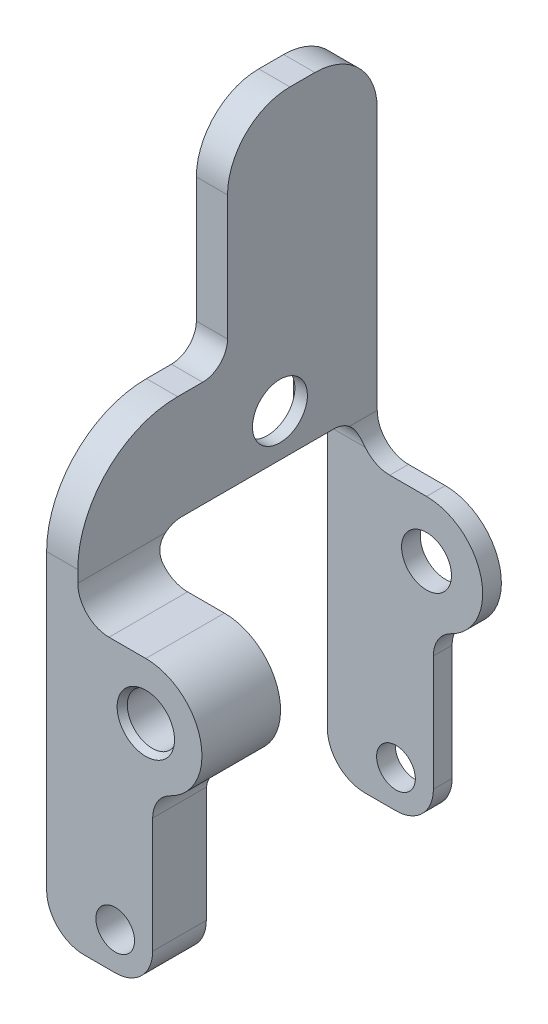
SolidWorks part; units mm, degrees
material "aluminio"
ref_plane "Alzado" through (0, 0, 0) normal (0, 0, 1) x (1, 0, 0)
ref_plane "Planta" through (0, 0, 0) normal (0, 1, 0) x (1, 0, 0)
ref_plane "Vista lateral" through (0, 0, 0) normal (1, 0, 0) x (0, 0, -1)
sketch "Croquis1" plane through (0, 0, 0) normal (0, 0, 1) x (1, 0, 0)
  line L0 (-5.5, 0) -> (-5.5, 31.5)
  line L1 (-5.5, 31.5) -> (-3, 31.5)
  line L2 (-3, 31.5) -> (-3, 20.05)
  line L3 (-3, 20.05) -> (2.45, 20.05)
  line L4 (0, -3) -> (-2.5, -3)
  line L5 (3, 0) -> (3, 11.0837)
  arc A0 (-5.5, 0) -> (-2.5, -3) centre (-2.5, 0) ccw
  arc A1 (3, 11.0837) -> (2.45, 20.05) centre (2.45, 15.55) ccw
  circle A2 centre (2.45, 15.55) radius 2
  circle A3 centre (0, 0) radius 1.55
  arc A5 (0, -3) -> (3, 0) centre (0, 0) ccw
  dimension "D1" = 5.5
  dimension "D2" = 31.5
  dimension "D4" = 9
  dimension "D7" = 4
  dimension "D8" = 3.1
  dimension "D9" = 3
  dimension "D12" = 3
  dimension "D3" = 2.5
  dimension "D5" = 15.55
  dimension "D6" = 2.45
extrude "Saliente-Extruir1" add sketch "Croquis1" along normal blind 24
sketch "Croquis2" plane through (-5.5, 0, 0) normal (-1, 0, 0) x (0, 0, 1)
  line L0 (24, -3) -> (0, -3) construction
  line L1 (1.5, -3) -> (19.7, -3)
  line L2 (1.5, -3) -> (1.5, 23)
  line L3 (1.5, 23) -> (17.7, 23)
  line L4 (17.7, 23) -> (17.7, 11)
  line L5 (1.5, 23) -> (0, 23) construction
  line L6 (0, 31.5) -> (0, 0) construction
  line L7 (0, 0) -> (0, -3) construction
  line L10 (17.7, 11) -> (19.7, 11)
  line L11 (19.7, 11) -> (19.7, -3)
  dimension "D1" = 16.2
  dimension "D2" = 26
  dimension "D3" = 1.5
  dimension "D4" = 12
  dimension "D5" = 2
extrude "Cortar-Extruir1" cut sketch "Croquis2" against normal blind 20
fillet "Redondeo1" radius 8 2 edges at (-4.25, 31.5, 0) (-4.25, 31.5, 24)
fillet "Redondeo2" radius 2 3 edges at (-1.25, 11, 19.7) (-4.25, 23, 17.7) (-4.25, 23, 1.5)
fillet "Redondeo5" radius 2.5 4 edges at (3, 11.0837, 0.75) (-3, 20.05, 20.85) (3, 11.0837, 20.85) (-3, 20.05, 0.75)
sketch "Croquis3" plane through (-5.5, 0, 0) normal (-1, 0, 0) x (0, 0, 1)
  line L0 (16, 31.5) -> (8, 31.5) construction
  line L1 (0, 23.5) -> (0, 0) construction
  circle A0 centre (7.8, 26.4) radius 2.2
  dimension "D1" = 4.4
  dimension "D2" = 5.1
  dimension "D3" = 7.8
extrude "Cortar-Extruir2" cut sketch "Croquis3" against normal blind 20
sketch "Croquis4" plane through (0, 23, 0) normal (0, -1, 0) x (1, 0, 0)
  line L0 (-5.5, 15.7) -> (-5.5, 3.5) construction
  line L1 (-5.5, 11.4) -> (-4, 11.4)
  line L2 (-5.5, 11.4) -> (-5.5, 4.2)
  line L3 (-5.5, 4.2) -> (-4, 4.2)
  line L4 (-4, 11.4) -> (-4, 4.2)
  line L5 (-5.5, 10) -> (-5.5, 5.6) construction
  point P8 (-5.5, 7.8)
  dimension "D1" = 7.2
  dimension "D2" = 1.5
extrude "Cortar-Extruir3" cut sketch "Croquis4" against normal blind 20
sketch "Croquis5" plane through (-5.5, 0, 0) normal (-1, 0, 0) x (0, 0, 1)
  line L0 (0, 23.5) -> (0, 48.5)
  line L1 (0, 48.5) -> (12, 48.5)
  line L2 (12, 30) -> (4.2, 30)
  line L5 (12, 30) -> (12, 48.5)
  line L6 (4.2, 30.5399) -> (4.2, 23) construction
  line L7 (4.2, 30) -> (0, 23.5)
  line L8 (8, 31.5) -> (11.4, 31.5) construction
  line L9 (16, 31.5) -> (11.4, 31.5) construction
  dimension "D1" = 4
  dimension "D2" = 1.5
  dimension "D3" = 17
extrude "Saliente-Extruir2" add sketch "Croquis5" against normal up to surface (2.5 mm away) up to face at (-3, 24.2, 7.8)
fillet "Redondeo7" radius 2 1 edges at (-4.25, 31.5, 12)
sketch "Croquis6" plane through (-5.5, 0, 0) normal (-1, 0, 0) x (0, 0, 1)
  line L0 (11.4, 30) -> (11.4, 23) construction
  line L1 (11.4, 28.5) -> (4.2, 28.5)
  line L2 (11.4, 28.5) -> (11.4, 31.5)
  line L3 (11.4, 31.5) -> (4.2, 31.5)
  line L4 (4.2, 28.5) -> (4.2, 31.5)
  line L5 (4.2, 30) -> (4.2, 23) construction
  line L6 (4.2, 23) -> (11.4, 23) construction
  dimension "D1" = 5.5
  dimension "D2" = 3
extrude "Cortar-Extruir4" cut sketch "Croquis6" against normal up to surface (1.5 mm away) up to face at (-4, 26.4, 5.6)
fillet "Redondeo8" radius 3 2 edges at (-4.75, 31.5, 11.4) (-4.75, 31.5, 4.2)
fillet "Redondeo9" radius 5 2 edges at (-4.25, 48.5, 0) (-4.25, 48.5, 12)
chamfer "Chaflán1" distance 0.3 angle 60 1 edges at (4.45, 15.55, 24) first distance on face at (4.45, 15.55, 24)
